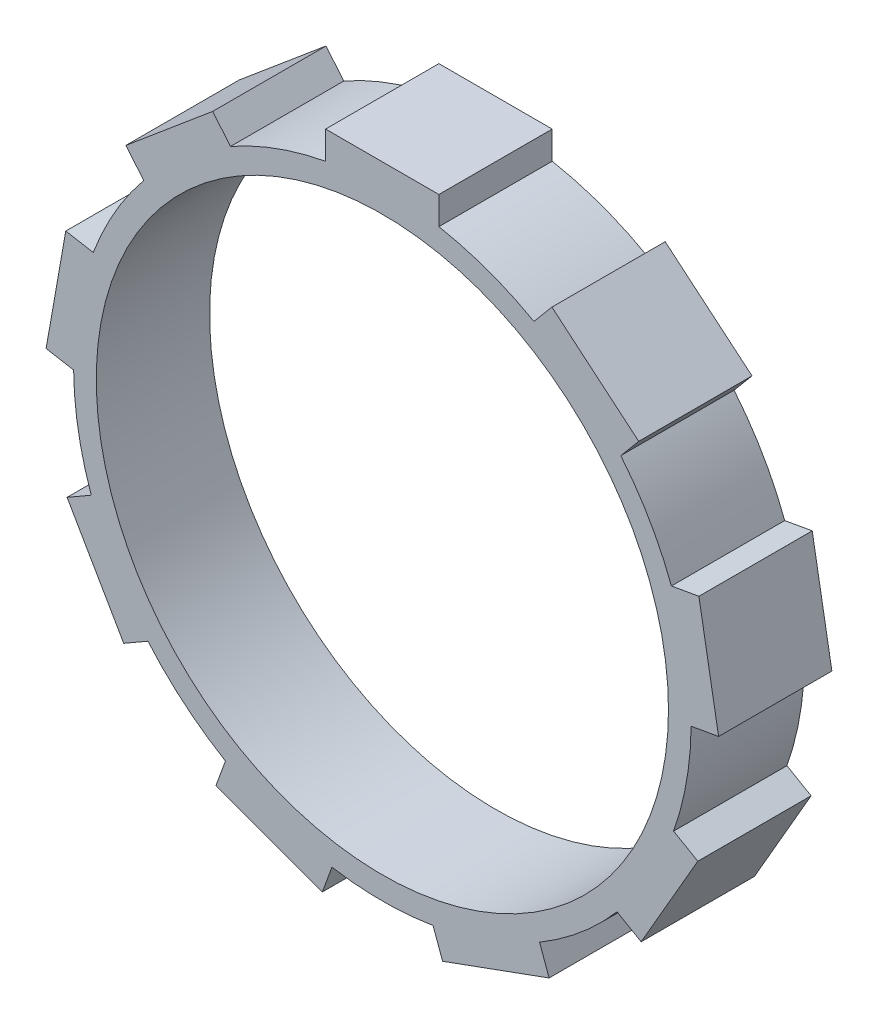
SolidWorks part; units mm, degrees
ref_plane "Alzado" through (0, 0, 0) normal (0, 0, 1) x (1, 0, 0)
ref_plane "Planta" through (0, 0, 0) normal (0, 1, 0) x (1, 0, 0)
ref_plane "Vista lateral" through (0, 0, 0) normal (1, 0, 0) x (0, 0, -1)
sketch "Croquis1" plane through (0, 0, 0) normal (0, 0, 1) x (1, 0, 0)
  line L0 (13.3778, 23.7402) -> (14.9622, 25.6284)
  line L2 (-5.0119, 26.7851) -> (-5.0119, 29.25)
  line L3 (-5.0119, 29.25) -> (4.9881, 29.25)
  line L4 (4.9881, 26.7896) -> (4.9881, 29.25)
  line L5 (-4.9879, 25.2501) -> (4.9881, 29.25) construction
  line L6 (-5.0119, 29.25) -> (4.9708, 25.2664) construction
  line L7 (14.9622, 25.6284) -> (22.6226, 19.2005)
  line L8 (21.0411, 17.3157) -> (22.6226, 19.2005)
  line L9 (25.5079, 9.587) -> (27.9353, 10.015)
  line L10 (27.9353, 10.015) -> (29.6718, 0.1669)
  line L11 (27.2488, -0.2603) -> (29.6718, 0.1669)
  line L12 (25.7026, -9.0521) -> (27.8372, -10.2845)
  line L13 (27.8372, -10.2845) -> (22.8372, -18.9448)
  line L14 (20.7064, -17.7146) -> (22.8372, -18.9448)
  line L15 (13.8707, -23.4556) -> (14.7138, -25.7718)
  line L16 (14.7138, -25.7718) -> (5.3168, -29.192)
  line L17 (4.4753, -26.88) -> (5.3168, -29.192)
  line L18 (-4.4514, -26.884) -> (-5.2944, -29.2002)
  line L19 (-5.2944, -29.2002) -> (-14.6913, -25.78)
  line L20 (-13.8498, -23.468) -> (-14.6913, -25.78)
  line L21 (-20.6906, -17.733) -> (-22.8253, -18.9655)
  line L22 (-22.8253, -18.9655) -> (-27.8253, -10.3052)
  line L23 (-25.6945, -9.075) -> (-27.8253, -10.3052)
  line L24 (-27.2485, -0.2846) -> (-29.6759, 0.1434)
  line L25 (-29.6759, 0.1434) -> (-27.9395, 9.9915)
  line L26 (-25.5164, 9.5642) -> (-27.9395, 9.9915)
  line L27 (-21.0565, 17.297) -> (-22.6409, 19.1852)
  line L28 (-22.6409, 19.1852) -> (-14.9805, 25.6131)
  line L29 (-13.3989, 23.7283) -> (-14.9805, 25.6131)
  circle A0 centre (0, 0) radius 25.25
  arc A1 (-5.0119, 26.7851) -> (-13.3989, 23.7283) centre (0, 0) ccw
  arc A2 (13.3778, 23.7402) -> (4.9881, 26.7896) centre (0, 0) ccw
  arc A3 (-21.0565, 17.297) -> (-25.5164, 9.5642) centre (0, 0) ccw
  arc A4 (-27.2485, -0.2846) -> (-25.6945, -9.075) centre (0, 0) ccw
  arc A5 (-20.6906, -17.733) -> (-13.8498, -23.468) centre (0, 0) ccw
  arc A6 (-4.4514, -26.884) -> (4.4753, -26.88) centre (0, 0) ccw
  arc A7 (13.8707, -23.4556) -> (20.7064, -17.7146) centre (0, 0) ccw
  arc A8 (25.7026, -9.0521) -> (27.2488, -0.2603) centre (0, 0) ccw
  arc A9 (25.5079, 9.587) -> (21.0411, 17.3157) centre (0, 0) ccw
  point P4 (0, 27.25)
  point P44 (0, 0)
  dimension "D1" = 50.5
  dimension "D2" = 2
  dimension "D4" = 4
  dimension "D5" = 10
  dimension "D3" = 9
extrude "Saliente-Extruir1" add sketch "Croquis1" along normal blind 10
